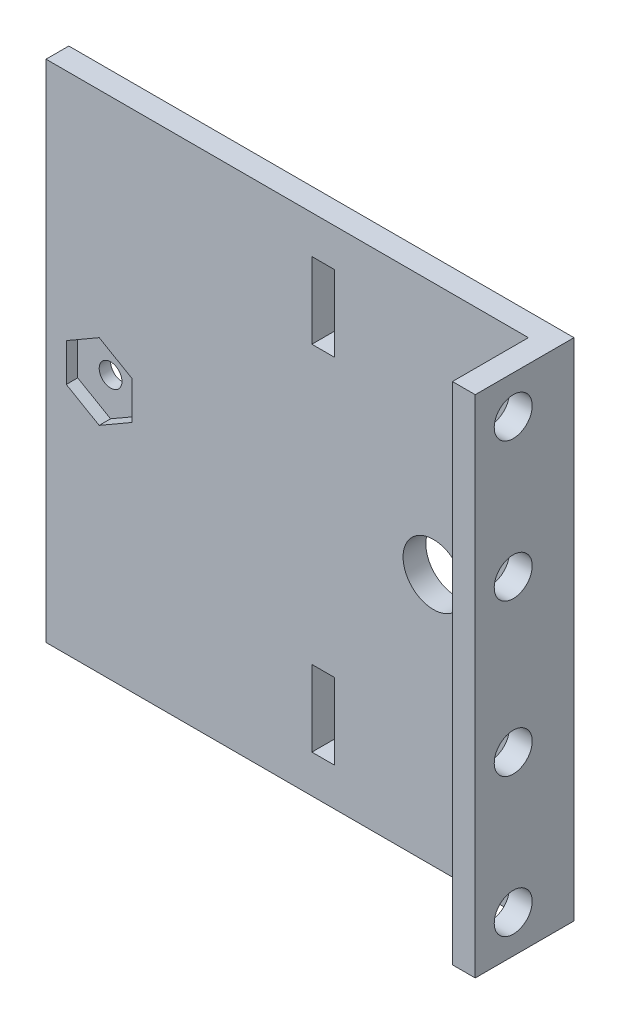
SolidWorks part; units mm, degrees
ref_plane "Front Plane" through (0, 0, 0) normal (0, 0, 1) x (1, 0, 0)
ref_plane "Top Plane" through (0, 0, 0) normal (0, 1, 0) x (1, 0, 0)
ref_plane "Right Plane" through (0, 0, 0) normal (1, 0, 0) x (0, 0, -1)
sketch "Sketch1" plane through (0, 0, 0) normal (0, 0, 1) x (1, 0, 0)
  line L1 (-33.25, 33.25) -> (33.25, 33.25)
  line L2 (-33.25, 33.25) -> (-33.25, -33.25)
  line L3 (-33.25, -33.25) -> (33.25, -33.25)
  line L4 (33.25, 33.25) -> (33.25, -33.25)
  line L5 (-33.25, 33.25) -> (33.25, -33.25) construction
  line L6 (-33.25, -33.25) -> (33.25, 33.25) construction
  circle A0 centre (17.75, 0) radius 4
  point P0 (0, 0)
  dimension "D4" = 8
  dimension "D1" = 66.5
  dimension "D2" = 66.5
  dimension "D3" = 15.5
  dimension "D5" = 33.25
extrude "Boss-Extrude1" add sketch "Sketch1" along normal blind 3
sketch "Sketch3" plane through (0, 0, 3) normal (0, 0, 1) x (1, 0, 0)
  line L0 (33.25, 33.25) -> (-33.25, 33.25) construction
  line L1 (33.25, -33.25) -> (30.25, -33.25)
  line L2 (33.25, -33.25) -> (33.25, 33.25)
  line L3 (33.25, 33.25) -> (30.25, 33.25)
  line L4 (30.25, -33.25) -> (30.25, 33.25)
  dimension "D1" = 3
extrude "Boss-Extrude2" add sketch "Sketch3" along normal blind 10
sketch "Sketch5" plane through (33.25, 0, 0) normal (1, 0, 0) x (0, 0, -1)
  line L0 (-13, -33.25) -> (0, -33.25) construction
  line L1 (-13, -33.25) -> (-13, 33.25) construction
  circle A0 centre (-8, -28.25) radius 2.5
  circle A1 centre (-8, -10) radius 2.5
  point P8 (-6.5, -33.25)
  dimension "D1" = 5
  dimension "D4" = 5
  dimension "D2" = 5
  dimension "D3" = 5
  dimension "D5" = 23.25
  dimension "D6" = 5
extrude "Cut-Extrude1" cut sketch "Sketch5" against normal up to next
mirror "Mirror2" about plane through (0, 0, 0) normal (0, 1, 0) of "Cut-Extrude1"
sketch "Sketch6" plane through (0, 0, 0) normal (0, 0, -1) x (-1, 0, 0)
  line L0 (-33.25, -33.25) -> (-33.25, 33.25) construction
  line L1 (-1.75, 28.25) -> (-4.75, 28.25)
  line L2 (-1.75, 28.25) -> (-1.75, 18.25)
  line L3 (-1.75, 18.25) -> (-4.75, 18.25)
  line L4 (-4.75, 28.25) -> (-4.75, 18.25)
  line L5 (-33.25, 33.25) -> (33.25, 33.25) construction
  dimension "D1" = 31.5
  dimension "D2" = 10
  dimension "D3" = 3
  dimension "D4" = 5
extrude "Cut-Extrude2" cut sketch "Sketch6" against normal up to next
mirror "Mirror3" about plane through (0, 0, 0) normal (0, 1, 0) of "Cut-Extrude2"
sketch "Sketch7" plane through (0, 0, 3) normal (0, 0, -1) x (-1, 0, 0)
  line L0 (7.15, 0) -> (-7.15, 0) construction
  line L1 (26.25, -5) -> (30.5801, -2.5)
  line L2 (30.5801, -2.5) -> (30.5801, 2.5)
  line L3 (30.5801, 2.5) -> (26.25, 5)
  line L4 (26.25, 5) -> (21.9199, 2.5)
  line L5 (21.9199, 2.5) -> (21.9199, -2.5)
  line L6 (21.9199, -2.5) -> (26.25, -5)
  line L7 (-33.25, -33.25) -> (-33.25, 33.25) construction
  circle A0 centre (26.25, 0) radius 4.3301 construction
  dimension "D1" = 5
  dimension "D2" = 59.5
extrude "Cut-Extrude5" cut sketch "Sketch7" along normal blind 1.5
sketch "Sketch9" plane through (0, 0, 0) normal (0, 0, -1) x (-1, 0, 0)
  line L0 (33.25, -33.25) -> (-33.25, -33.25) construction
  line L1 (-33.25, -33.25) -> (-33.25, 33.25) construction
  circle A0 centre (26.25, 0) radius 1.5
  dimension "D1" = 3
  dimension "D2" = 33.25
  dimension "D3" = 59.5
extrude "Cut-Extrude6" cut sketch "Sketch9" against normal up to next
